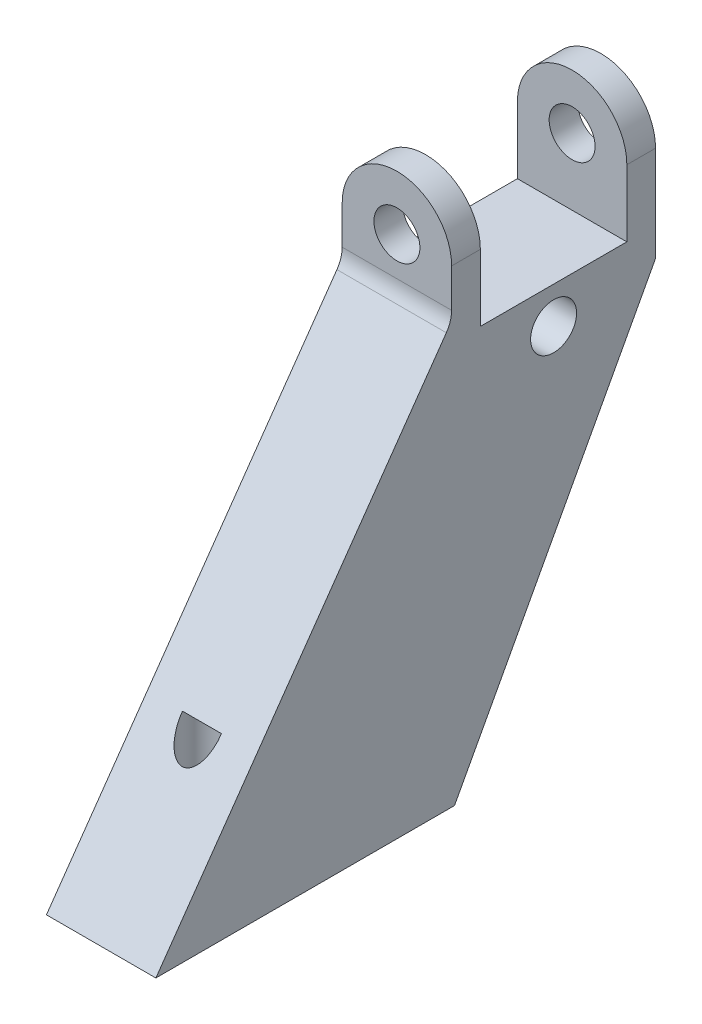
SolidWorks part; units mm, degrees
ref_plane "Front Plane" through (0, 0, 0) normal (0, 0, 1) x (1, 0, 0)
ref_plane "Top Plane" through (0, 0, 0) normal (0, 1, 0) x (1, 0, 0)
ref_plane "Right Plane" through (0, 0, 0) normal (1, 0, 0) x (0, 0, -1)
sketch "Sketch6" plane through (0, 3.4314, 0) normal (0, 1, 0) x (-1, 0, 0)
  line L0 (-13.5144, 0) -> (5.5356, 0)
  line L5 (-7.9894, 155.54) -> (0.0106, 155.54) construction
  line L8 (5.5356, 0) -> (5.5356, 133.908)
  line L9 (5.5356, 133.908) -> (-13.5144, 133.908)
  line L10 (-13.5144, 0) -> (-13.5144, 133.908)
  line L17 (-7.9894, 155.54) -> (0.0106, 155.54) construction
  line L18 (-3.9894, 155.54) -> (-3.9894, 0) construction
  dimension "D1" = 19.05
sketch3d "3DSketch1" [suppressed]
  circle A0 centre (4.1661, 92.3902, 4.7625) radius 4 construction
  circle A1 centre (4.1661, 92.3902, 4.7625) radius 4
  circle A2 centre (4.1661, 92.3902, 30.1625) radius 4 construction
  circle A3 centre (4.1661, 92.3902, 30.1625) radius 4
  point P2 (4.1661, 92.3902, 8.7625)
  point P4 (4.1661, 92.3902, 8.7625)
  point P7 (4.1661, 92.3902, 34.1625)
  point P9 (4.1661, 92.3902, 34.1625)
extrude "Boss-Extrude5" add sketch "Sketch6" along normal blind 101.6
sketch "Sketch9" plane through (0, 0, 0) normal (0, 0, -1) x (-1, 0, 0)
  line L1 (-13.5144, 105.0314) -> (6.0586, 105.0314)
  line L2 (-13.5144, 105.0314) -> (-13.5144, 87.861)
  line L3 (-13.5144, 87.861) -> (6.0586, 87.861)
  line L12 (6.0586, 105.0314) -> (6.0586, 87.861)
extrude "Cut-Extrude5" [suppressed] cut sketch "Sketch9" against normal through all
sketch "Sketch10" plane through (13.5144, 0, 0) normal (1, 0, 0) x (0, 0, -1)
  line L0 (-87, 3.4314) -> (-167.5984, 3.4314)
  line L1 (-133.908, 3.4314) -> (0, 3.4314) construction
  line L2 (-167.5984, 3.4314) -> (-168.5558, 132.8824)
  line L3 (-168.5558, 132.8824) -> (-35.5045, 117.0228)
  line L4 (-35.5045, 117.0228) -> (-35.5045, 78.3573)
  line L5 (-36.4274, 75.4376) -> (-87, 3.4314)
  line L6 (-35, 3.4314) -> (7.4334, 3.4314)
  line L7 (7.4334, 3.4314) -> (7.4334, 68.4314)
  line L8 (7.4334, 68.4314) -> (0, 68.4314)
  line L9 (0, 68.4314) -> (-35, 3.4314)
  line L10 (0, 105.0314) -> (0, 3.4314) construction
  line L12 (-30.5045, 96.7069) -> (-5, 96.7069)
  line L13 (-30.5045, 96.7069) -> (-30.5045, 73.4314)
  line L14 (-30.5045, 73.4314) -> (-5, 73.4314)
  line L15 (-5, 96.7069) -> (-5, 73.4314)
  arc A0 (-35.5045, 78.3573) -> (-36.4274, 75.4376) centre (-40.5845, 78.3573) cw
  point P22 (-30.5045, 85.0692)
  dimension "D8" = 5.08
  dimension "D1" = 5
  dimension "D2" = 5
  dimension "D3" = 65
  dimension "D4" = 35
  dimension "D5" = 52
  dimension "D6" = 25.5045
  dimension "D7" = 70
extrude "Cut-Extrude6" cut sketch "Sketch10" against normal through all
sketch "Sketch12" plane through (0, 0, 35.5045) normal (0, 0, 1) x (1, 0, 0)
  line L0 (3.9894, 3.4314) -> (3.9894, 85.0528) construction
  line L1 (7.9894, 3.4314) -> (-0.0106, 3.4314) construction
  line L2 (-5.5356, 85.0528) -> (13.5144, 85.0528) construction
  line L3 (-5.5356, 78.3573) -> (-5.5356, 105.0314) construction
  line L4 (13.5144, 78.3573) -> (13.5144, 105.0314) construction
  line L5 (13.5144, 85.0528) -> (39.9433, 85.0528)
  line L6 (39.9433, 85.0528) -> (39.9433, 114.8081)
  line L7 (39.9433, 114.8081) -> (-16.1264, 114.8081)
  line L8 (-16.1264, 114.8081) -> (-16.1264, 85.0528)
  line L9 (-16.1264, 85.0528) -> (-5.5356, 85.0528)
  circle A0 centre (3.9894, 85.0528) radius 4
  arc A1 (13.5144, 85.0528) -> (-5.5356, 85.0528) centre (3.9894, 85.0528) ccw
  dimension "D2" = 8
  dimension "D1" = 81.6214
extrude "Cut-Extrude7" cut sketch "Sketch12" against normal through all
sketch "Sketch13" plane through (0, 3.4314, 0) normal (0, -1, 0) x (1, 0, 0)
  line L0 (3.9894, 87) -> (3.9894, 69.5) construction
  line L1 (-5.5356, 87) -> (13.5144, 87) construction
  line L2 (3.9894, 155.54) -> (3.9894, 0) construction
  line L3 (3.9894, 69.5) -> (3.9894, 42.5) construction
  dimension "D1" = 17.5
  dimension "D2" = 27
sketch "Sketch14" plane through (0, 3.4314, 0) normal (0, -1, 0) x (1, 0, 0)
  circle A0 centre (3.9894, 69.5) radius 3.4
  circle A1 centre (3.9894, 42.5) radius 3.4
  dimension "D1" = 6.8
extrude "Cut-Extrude8" cut sketch "Sketch14" against normal blind 25
thread "Thread1" pitch 1.25 method cut profile "Thread Profile1" start angle 0, offset 0, length 15, pitch 1.25, diameter 6.8
ref_plane "Plane1" through (7.3894, 3.4314, 42.5) normal (0, 0, 1) x (1, 0, 0)
sketch "Thread Profile1" plane through (7.3894, 3.4314, 42.5) normal (0, 0, 1) x (1, 0, 0)
  line L0 (0, 0) -> (0, 1.25) construction
  line L1 (0, 0) -> (0.6766, 0.3906)
  line L2 (0.6766, 0.3906) -> (0.6766, 0.5469)
  line L3 (0.6766, 0.5469) -> (0, 0.9375)
  line L4 (0.6766, 0.4687) -> (0, 0.4687) construction
  line L11 (0, 0) -> (0, 0.9375)
  point P2 (0, 0)
  dimension "Pitch" = 1.25
  dimension "Profile_Angle" = 60
  dimension "Profile_Land" = 0.1562
  dimension "Profile_Height" = 0.6766
thread "Thread2" pitch 1.25 method cut profile "Thread Profile2" start angle 0, offset 0, length 15, pitch 1.25, diameter 6.8
ref_plane "Plane2" through (7.3894, 3.4314, 69.5) normal (0, 0, 1) x (1, 0, 0)
sketch "Thread Profile2" plane through (7.3894, 3.4314, 69.5) normal (0, 0, 1) x (1, 0, 0)
  line L0 (0, 0) -> (0, 1.25) construction
  line L1 (0, 0) -> (0.6766, 0.3906)
  line L2 (0.6766, 0.3906) -> (0.6766, 0.5469)
  line L3 (0.6766, 0.5469) -> (0, 0.9375)
  line L4 (0.6766, 0.4687) -> (0, 0.4687) construction
  line L11 (0, 0) -> (0, 0.9375)
  point P2 (0, 0)
  dimension "Pitch" = 1.25
  dimension "Profile_Angle" = 60
  dimension "Profile_Land" = 0.1562
  dimension "Profile_Height" = 0.6766
sketch "Sketch19" plane through (13.5144, 0, 0) normal (1, 0, 0) x (0, 0, -1)
  line L0 (-17.7522, 73.4314) -> (-17.7522, 67.0814) construction
  line L1 (-30.5045, 73.4314) -> (-5, 73.4314) construction
  circle A0 centre (-17.7522, 67.0814) radius 4
  dimension "D1" = 6.35
  dimension "D2" = 8
extrude "Cut-Extrude9" cut sketch "Sketch19" against normal through all
